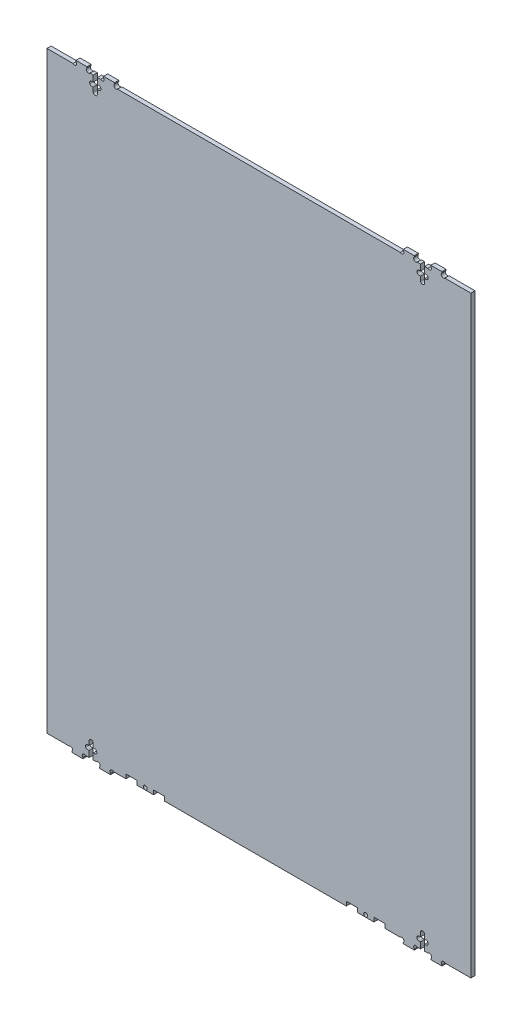
SolidWorks part; units mm, degrees
ref_plane "Спереди" through (0, 0, 0) normal (0, 0, 1) x (1, 0, 0)
ref_plane "Сверху" through (0, 0, 0) normal (0, 1, 0) x (1, 0, 0)
ref_plane "Справа" through (0, 0, 0) normal (1, 0, 0) x (0, 0, -1)
other "Configuration Table"
sketch "Эскиз2" plane through (0, 0, 0) normal (0, 0, 1) x (1, 0, 0)
  line L1 (1138.3, -435.8) -> (518, -435.8)
  line L2 (1138.3, -435.8) -> (1138.3, 435.8)
  line L3 (1138.3, 435.8) -> (518, 435.8)
  line L11 (518, -435.8) -> (518, 435.8)
  dimension "X001" = 518
  dimension "X002" = 1138.3
  dimension "Y001" = 435.8
  dimension "Y002" = 435.8
extrude "Бобышка-Вытянуть1" add sketch "Эскиз2" against normal blind 6
sketch "Стыки_эскиз_пазов_и_стяжек_М5" plane through (0, 0, 0) normal (0, 0, 1) x (1, 0, 0)
  line L0 (1138.4, 429.8) -> (1138.4, 435.8)
  line L1 (1138.4, 435.8) -> (1096.3, 435.8)
  line L2 (1096.3, 435.8) -> (1096.3, 429.8)
  line L3 (1096.3, 429.8) -> (1138.4, 429.8)
  line L4 (678.425, -423.725) -> (678.425, -429.8)
  line L5 (678.425, -429.8) -> (654.575, -429.8)
  line L6 (654.575, -429.8) -> (654.575, -423.725)
  line L7 (654.575, -423.725) -> (638.425, -423.725)
  line L8 (638.425, -423.725) -> (638.425, -429.8)
  line L9 (638.425, -429.8) -> (616, -429.8)
  line L10 (616, -429.8) -> (616, -435.8)
  line L11 (616, -435.8) -> (1040.3, -435.8)
  line L12 (1040.3, -435.8) -> (1040.3, -429.8)
  line L13 (1040.3, -429.8) -> (1013.875, -429.8)
  line L14 (1013.875, -429.8) -> (1013.875, -423.725)
  line L15 (1013.875, -423.725) -> (997.725, -423.725)
  line L16 (997.725, -423.725) -> (997.725, -429.8)
  line L17 (997.725, -429.8) -> (973.875, -429.8)
  line L18 (973.875, -429.8) -> (973.875, -423.725)
  line L19 (973.875, -423.725) -> (957.725, -423.725)
  line L20 (957.725, -423.725) -> (957.725, -429.8)
  line L21 (957.725, -429.8) -> (694.575, -429.8)
  line L22 (694.575, -429.8) -> (694.575, -423.725)
  line L23 (694.575, -423.725) -> (678.425, -423.725)
  line L24 (590.75, -419.95) -> (592.15, -419.95)
  line L25 (592.15, -419.95) -> (592.15, -415.65)
  line L26 (592.15, -415.65) -> (590.75, -415.65)
  line L27 (590.75, -415.65) -> (590.75, -408.8)
  line L28 (590.75, -408.8) -> (585.25, -408.8)
  line L29 (585.25, -408.8) -> (585.25, -415.65)
  line L30 (585.25, -415.65) -> (583.85, -415.65)
  line L31 (583.85, -415.65) -> (583.85, -419.95)
  line L32 (583.85, -419.95) -> (585.25, -419.95)
  line L33 (585.25, -419.95) -> (585.25, -429.8)
  line L34 (585.25, -429.8) -> (576, -429.8)
  line L35 (576, -429.8) -> (576, -435.8)
  line L36 (576, -435.8) -> (585.25, -435.8)
  line L37 (585.25, -435.8) -> (585.25, -435.9)
  line L38 (585.25, -435.9) -> (590.75, -435.9)
  line L39 (590.75, -435.9) -> (590.75, -435.8)
  line L40 (590.75, -435.8) -> (600, -435.8)
  line L41 (600, -435.8) -> (600, -429.8)
  line L42 (600, -429.8) -> (590.75, -429.8)
  line L43 (590.75, -429.8) -> (590.75, -419.95)
  line L44 (518, 435.8) -> (518, -429.8)
  line L45 (518, -429.8) -> (517.9, -429.8)
  line L46 (517.9, -429.8) -> (517.9, -435.8)
  line L47 (517.9, -435.8) -> (560, -435.8)
  line L48 (560, -435.8) -> (560, -429.8)
  line L49 (560, -429.8) -> (524, -429.8)
  line L50 (524, -429.8) -> (524, 429.8)
  line L51 (524, 429.8) -> (566, 429.8)
  line L52 (566, 429.8) -> (566, 435.8)
  line L53 (566, 435.8) -> (518, 435.8)
  line L54 (1040.3, 429.8) -> (1040.3, 435.8)
  line L55 (1040.3, 435.8) -> (622, 435.8)
  line L56 (622, 435.8) -> (622, 429.8)
  line L57 (622, 429.8) -> (1040.3, 429.8)
  line L58 (1065.55, -435.8) -> (1065.55, -435.9)
  line L59 (1065.55, -435.9) -> (1071.05, -435.9)
  line L60 (1071.05, -435.9) -> (1071.05, -435.8)
  line L61 (1071.05, -435.8) -> (1080.3, -435.8)
  line L62 (1080.3, -435.8) -> (1080.3, -429.8)
  line L63 (1080.3, -429.8) -> (1071.05, -429.8)
  line L64 (1071.05, -429.8) -> (1071.05, -419.95)
  line L65 (1071.05, -419.95) -> (1072.45, -419.95)
  line L66 (1072.45, -419.95) -> (1072.45, -415.65)
  line L67 (1072.45, -415.65) -> (1071.05, -415.65)
  line L68 (1071.05, -415.65) -> (1071.05, -408.8)
  line L69 (1071.05, -408.8) -> (1065.55, -408.8)
  line L70 (1065.55, -408.8) -> (1065.55, -415.65)
  line L71 (1065.55, -415.65) -> (1064.15, -415.65)
  line L72 (1064.15, -415.65) -> (1064.15, -419.95)
  line L73 (1064.15, -419.95) -> (1065.55, -419.95)
  line L74 (1065.55, -419.95) -> (1065.55, -429.8)
  line L75 (1065.55, -429.8) -> (1056.3, -429.8)
  line L76 (1056.3, -429.8) -> (1056.3, -435.8)
  line L77 (1056.3, -435.8) -> (1065.55, -435.8)
  line L78 (1071.05, 415.65) -> (1072.45, 415.65)
  line L79 (1072.45, 415.65) -> (1072.45, 419.95)
  line L80 (1072.45, 419.95) -> (1071.05, 419.95)
  line L81 (1071.05, 419.95) -> (1071.05, 429.8)
  line L82 (1071.05, 429.8) -> (1080.3, 429.8)
  line L83 (1080.3, 429.8) -> (1080.3, 435.8)
  line L84 (1080.3, 435.8) -> (1071.05, 435.8)
  line L85 (1071.05, 435.8) -> (1071.05, 435.9)
  line L86 (1071.05, 435.9) -> (1065.55, 435.9)
  line L87 (1065.55, 435.9) -> (1065.55, 435.8)
  line L88 (1065.55, 435.8) -> (1056.3, 435.8)
  line L89 (1056.3, 435.8) -> (1056.3, 429.8)
  line L90 (1056.3, 429.8) -> (1065.55, 429.8)
  line L91 (1065.55, 429.8) -> (1065.55, 419.95)
  line L92 (1065.55, 419.95) -> (1064.15, 419.95)
  line L93 (1064.15, 419.95) -> (1064.15, 415.65)
  line L94 (1064.15, 415.65) -> (1065.55, 415.65)
  line L95 (1065.55, 415.65) -> (1065.55, 408.8)
  line L96 (1065.55, 408.8) -> (1071.05, 408.8)
  line L97 (1071.05, 408.8) -> (1071.05, 415.65)
  line L98 (596.75, 435.8) -> (596.75, 435.9)
  line L99 (596.75, 435.9) -> (591.25, 435.9)
  line L100 (591.25, 435.9) -> (591.25, 435.8)
  line L101 (591.25, 435.8) -> (582, 435.8)
  line L102 (582, 435.8) -> (582, 429.8)
  line L103 (582, 429.8) -> (591.25, 429.8)
  line L104 (591.25, 429.8) -> (591.25, 419.95)
  line L105 (591.25, 419.95) -> (589.85, 419.95)
  line L106 (589.85, 419.95) -> (589.85, 415.65)
  line L107 (589.85, 415.65) -> (591.25, 415.65)
  line L108 (591.25, 415.65) -> (591.25, 408.8)
  line L109 (591.25, 408.8) -> (596.75, 408.8)
  line L110 (596.75, 408.8) -> (596.75, 415.65)
  line L111 (596.75, 415.65) -> (598.15, 415.65)
  line L112 (598.15, 415.65) -> (598.15, 419.95)
  line L113 (598.15, 419.95) -> (596.75, 419.95)
  line L114 (596.75, 419.95) -> (596.75, 429.8)
  line L115 (596.75, 429.8) -> (606, 429.8)
  line L116 (606, 429.8) -> (606, 435.8)
  line L117 (606, 435.8) -> (596.75, 435.8)
  line L118 (1096.3, -435.8) -> (1138.4, -435.8)
  line L119 (1138.4, -435.8) -> (1138.4, -429.8)
  line L120 (1138.4, -429.8) -> (1096.3, -429.8)
  line L121 (1096.3, -429.8) -> (1096.3, -435.8)
  circle A0 centre (666.5, -426.8) radius 2.75
  circle A1 centre (985.8, -426.8) radius 2.75
  dimension "Диаметр001" = 5.5
  dimension "Диаметр002" = 5.5
  dimension "X001" = 517.9
  dimension "X002" = 518
  dimension "X003" = 524
  dimension "X004" = 560
  dimension "X005" = 566
  dimension "X006" = 576
  dimension "X007" = 582
  dimension "X008" = 583.85
  dimension "X009" = 585.25
  dimension "X010" = 589.85
  dimension "X011" = 590.75
  dimension "X012" = 591.25
  dimension "X013" = 592.15
  dimension "X014" = 596.75
  dimension "X015" = 598.15
  dimension "X016" = 600
  dimension "X017" = 606
  dimension "X018" = 616
  dimension "X019" = 622
  dimension "X020" = 638.425
  dimension "X021" = 654.575
  dimension "X022" = 666.5
  dimension "X023" = 678.425
  dimension "X024" = 694.575
  dimension "X025" = 957.725
  dimension "X026" = 973.875
  dimension "X027" = 985.8
  dimension "X028" = 997.725
  dimension "X029" = 1013.875
  dimension "X030" = 1040.3
  dimension "X031" = 1056.3
  dimension "X032" = 1064.15
  dimension "X033" = 1065.55
  dimension "X034" = 1071.05
  dimension "X035" = 1072.45
  dimension "X036" = 1080.3
  dimension "X037" = 1096.3
  dimension "X038" = 1138.4
  dimension "Y001" = 435.9
  dimension "Y002" = 435.8
  dimension "Y003" = 429.8
  dimension "Y004" = 426.8
  dimension "Y005" = 423.725
  dimension "Y006" = 419.95
  dimension "Y007" = 415.65
  dimension "Y008" = 408.8
  dimension "Y009" = 408.8
  dimension "Y010" = 415.65
  dimension "Y011" = 419.95
  dimension "Y012" = 429.8
  dimension "Y013" = 435.8
  dimension "Y014" = 435.9
extrude "Стыки_шип_паз_стяжки_М5" cut sketch "Стыки_эскиз_пазов_и_стяжек_М5" against normal through all and the other way through all
sketch "ЧПУ_М6_01_Центр" plane through (0, 0, 0) normal (0, 0, 1) x (1, 0, 0)
  line L0 (1064.15, -415.65) -> (1064.15, -419.95) construction
  line L1 (1071.05, -419.95) -> (1072.45, -419.95) construction
  point P0 (1068.3, -417.8)
  dimension "От_кромки_по_X" = 4.15
  dimension "От_кромки_по_Y" = 2.15
sketch "ЧПУ_М6_01_Канал_эскиз" plane through (0, 0, 0) normal (0, 0, 1) x (1, 0, 0)
  line L0 (1065.3, -429.9) -> (1071.3, -429.9)
  line L1 (1071.3, -429.9) -> (1071.3, -408.7)
  line L2 (1071.3, -408.7) -> (1065.3, -408.7)
  line L3 (1065.3, -408.7) -> (1065.3, -429.9)
  line L4 (1065.3, -429.9) -> (1071.3, -408.7) construction
  point P4 (1068.3, -419.3)
  dimension "Ширина" = 6
  dimension "Глубина" = 21.2
  dimension "Положение_ОтКромки" = 1.5
extrude "ЧПУ_М6_01_Канал" cut sketch "ЧПУ_М6_01_Канал_эскиз" against normal through all and the other way through all
sketch "ЧПУ_М6_01_Гайка_эскиз" plane through (0, 0, 0) normal (0, 0, 1) x (1, 0, 0)
  line L0 (1063.15, -420.9) -> (1073.45, -420.9)
  line L1 (1073.45, -420.9) -> (1073.45, -414.7)
  line L2 (1073.45, -414.7) -> (1063.15, -414.7)
  line L3 (1063.15, -414.7) -> (1063.15, -420.9)
  line L4 (1063.15, -420.9) -> (1073.45, -414.7) construction
  point P4 (1068.3, -417.8)
  dimension "Ширина" = 10.3
  dimension "Глубина" = 6.2
extrude "ЧПУ_М6_01_Гайка" cut sketch "ЧПУ_М6_01_Гайка_эскиз" against normal through all and the other way through all
sketch "ЧПУ_М6_01_Т_эскиз_1" plane through (0, 0, 0) normal (0, 0, 1) x (1, 0, 0)
  circle A0 centre (1073.45, -417.75) radius 3.05
  circle A1 centre (1063.15, -417.75) radius 3.05
  dimension "Диаметр1" = 6.1
  dimension "Диаметр2" = 6.1
  dimension "Центр1_ПоОси" = 5.15
  dimension "Центр1_ОтКромки" = 0.05
  dimension "Центр2_ПоОси" = 5.15
  dimension "Центр2_ОтКромки" = 0.05
extrude "ЧПУ_М6_01_Т_разгрузка_1" cut sketch "ЧПУ_М6_01_Т_эскиз_1" against normal through all and the other way through all
sketch "ЧПУ_М6_01_Т_эскиз_-1" plane through (0, 0, 0) normal (0, 0, 1) x (1, 0, 0)
  circle A0 centre (1073.45, -417.85) radius 3.05
  circle A1 centre (1063.15, -417.85) radius 3.05
  dimension "Диаметр1" = 6.1
  dimension "Диаметр2" = 6.1
  dimension "Центр1_ПоОси" = 5.15
  dimension "Центр1_ОтКромки" = 0.05
  dimension "Центр2_ПоОси" = 5.15
  dimension "Центр2_ОтКромки" = 0.05
extrude "ЧПУ_М6_01_Т_разгрузка_-1" cut sketch "ЧПУ_М6_01_Т_эскиз_-1" against normal through all and the other way through all
sketch "ЧПУ_М6_01_Конец_эскиз" plane through (0, 0, 0) normal (0, 0, 1) x (1, 0, 0)
  circle A0 centre (1068.3, -408.7) radius 3
  dimension "Центр1_ОтКромки" = 9.1
extrude "ЧПУ_М6_01_Конец" cut sketch "ЧПУ_М6_01_Конец_эскиз" against normal through all and the other way through all
sketch "ЧПУ_М6_02_Центр" plane through (0, 0, 0) normal (0, 0, 1) x (1, 0, 0)
  line L0 (1064.15, 419.95) -> (1064.15, 415.65) construction
  line L1 (1064.15, 415.65) -> (1065.55, 415.65) construction
  point P0 (1068.3, 417.8)
  dimension "От_кромки_по_X" = 4.15
  dimension "От_кромки_по_Y" = 2.15
sketch "ЧПУ_М6_02_Канал_эскиз" plane through (0, 0, 0) normal (0, 0, 1) x (1, 0, 0)
  line L0 (1065.3, 408.7) -> (1071.3, 408.7)
  line L1 (1071.3, 408.7) -> (1071.3, 429.9)
  line L2 (1071.3, 429.9) -> (1065.3, 429.9)
  line L3 (1065.3, 429.9) -> (1065.3, 408.7)
  line L4 (1065.3, 408.7) -> (1071.3, 429.9) construction
  point P4 (1068.3, 419.3)
  dimension "Ширина" = 6
  dimension "Глубина" = 21.2
  dimension "Положение_ОтКромки" = 1.5
extrude "ЧПУ_М6_02_Канал" cut sketch "ЧПУ_М6_02_Канал_эскиз" against normal through all and the other way through all
sketch "ЧПУ_М6_02_Гайка_эскиз" plane through (0, 0, 0) normal (0, 0, 1) x (1, 0, 0)
  line L0 (1063.15, 414.7) -> (1073.45, 414.7)
  line L1 (1073.45, 414.7) -> (1073.45, 420.9)
  line L2 (1073.45, 420.9) -> (1063.15, 420.9)
  line L3 (1063.15, 420.9) -> (1063.15, 414.7)
  line L4 (1063.15, 414.7) -> (1073.45, 420.9) construction
  point P4 (1068.3, 417.8)
  dimension "Ширина" = 10.3
  dimension "Глубина" = 6.2
extrude "ЧПУ_М6_02_Гайка" cut sketch "ЧПУ_М6_02_Гайка_эскиз" against normal through all and the other way through all
sketch "ЧПУ_М6_02_Т_эскиз_1" plane through (0, 0, 0) normal (0, 0, 1) x (1, 0, 0)
  circle A0 centre (1073.45, 417.85) radius 3.05
  circle A1 centre (1063.15, 417.85) radius 3.05
  dimension "Диаметр1" = 6.1
  dimension "Диаметр2" = 6.1
  dimension "Центр1_ПоОси" = 5.15
  dimension "Центр1_ОтКромки" = 0.05
  dimension "Центр2_ПоОси" = 5.15
  dimension "Центр2_ОтКромки" = 0.05
extrude "ЧПУ_М6_02_Т_разгрузка_1" cut sketch "ЧПУ_М6_02_Т_эскиз_1" against normal through all and the other way through all
sketch "ЧПУ_М6_02_Т_эскиз_-1" plane through (0, 0, 0) normal (0, 0, 1) x (1, 0, 0)
  circle A0 centre (1073.45, 417.75) radius 3.05
  circle A1 centre (1063.15, 417.75) radius 3.05
  dimension "Диаметр1" = 6.1
  dimension "Диаметр2" = 6.1
  dimension "Центр1_ПоОси" = 5.15
  dimension "Центр1_ОтКромки" = 0.05
  dimension "Центр2_ПоОси" = 5.15
  dimension "Центр2_ОтКромки" = 0.05
extrude "ЧПУ_М6_02_Т_разгрузка_-1" cut sketch "ЧПУ_М6_02_Т_эскиз_-1" against normal through all and the other way through all
sketch "ЧПУ_М6_02_Конец_эскиз" plane through (0, 0, 0) normal (0, 0, 1) x (1, 0, 0)
  circle A0 centre (1068.3, 408.7) radius 3
  dimension "Центр1_ОтКромки" = 9.1
extrude "ЧПУ_М6_02_Конец" cut sketch "ЧПУ_М6_02_Конец_эскиз" against normal through all and the other way through all
sketch "ЧПУ_М6_03_Центр" plane through (0, 0, 0) normal (0, 0, 1) x (1, 0, 0)
  line L0 (589.85, 419.95) -> (589.85, 415.65) construction
  line L1 (589.85, 415.65) -> (591.25, 415.65) construction
  point P0 (594, 417.8)
  dimension "От_кромки_по_X" = 4.15
  dimension "От_кромки_по_Y" = 2.15
sketch "ЧПУ_М6_03_Канал_эскиз" plane through (0, 0, 0) normal (0, 0, 1) x (1, 0, 0)
  line L0 (591, 408.7) -> (597, 408.7)
  line L1 (597, 408.7) -> (597, 429.9)
  line L2 (597, 429.9) -> (591, 429.9)
  line L3 (591, 429.9) -> (591, 408.7)
  line L4 (591, 408.7) -> (597, 429.9) construction
  point P4 (594, 419.3)
  dimension "Ширина" = 6
  dimension "Глубина" = 21.2
  dimension "Положение_ОтКромки" = 1.5
extrude "ЧПУ_М6_03_Канал" cut sketch "ЧПУ_М6_03_Канал_эскиз" against normal through all and the other way through all
sketch "ЧПУ_М6_03_Гайка_эскиз" plane through (0, 0, 0) normal (0, 0, 1) x (1, 0, 0)
  line L0 (588.85, 414.7) -> (599.15, 414.7)
  line L1 (599.15, 414.7) -> (599.15, 420.9)
  line L2 (599.15, 420.9) -> (588.85, 420.9)
  line L3 (588.85, 420.9) -> (588.85, 414.7)
  line L4 (588.85, 414.7) -> (599.15, 420.9) construction
  point P4 (594, 417.8)
  dimension "Ширина" = 10.3
  dimension "Глубина" = 6.2
extrude "ЧПУ_М6_03_Гайка" cut sketch "ЧПУ_М6_03_Гайка_эскиз" against normal through all and the other way through all
sketch "ЧПУ_М6_03_Т_эскиз_1" plane through (0, 0, 0) normal (0, 0, 1) x (1, 0, 0)
  circle A0 centre (599.15, 417.85) radius 3.05
  circle A1 centre (588.85, 417.85) radius 3.05
  dimension "Диаметр1" = 6.1
  dimension "Диаметр2" = 6.1
  dimension "Центр1_ПоОси" = 5.15
  dimension "Центр1_ОтКромки" = 0.05
  dimension "Центр2_ПоОси" = 5.15
  dimension "Центр2_ОтКромки" = 0.05
extrude "ЧПУ_М6_03_Т_разгрузка_1" cut sketch "ЧПУ_М6_03_Т_эскиз_1" against normal through all and the other way through all
sketch "ЧПУ_М6_03_Т_эскиз_-1" plane through (0, 0, 0) normal (0, 0, 1) x (1, 0, 0)
  circle A0 centre (599.15, 417.75) radius 3.05
  circle A1 centre (588.85, 417.75) radius 3.05
  dimension "Диаметр1" = 6.1
  dimension "Диаметр2" = 6.1
  dimension "Центр1_ПоОси" = 5.15
  dimension "Центр1_ОтКромки" = 0.05
  dimension "Центр2_ПоОси" = 5.15
  dimension "Центр2_ОтКромки" = 0.05
extrude "ЧПУ_М6_03_Т_разгрузка_-1" cut sketch "ЧПУ_М6_03_Т_эскиз_-1" against normal through all and the other way through all
sketch "ЧПУ_М6_03_Конец_эскиз" plane through (0, 0, 0) normal (0, 0, 1) x (1, 0, 0)
  circle A0 centre (594, 408.7) radius 3
  dimension "Центр1_ОтКромки" = 9.1
extrude "ЧПУ_М6_03_Конец" cut sketch "ЧПУ_М6_03_Конец_эскиз" against normal through all and the other way through all
sketch "ЧПУ_М6_04_Центр" plane through (0, 0, 0) normal (0, 0, 1) x (1, 0, 0)
  line L0 (583.85, -415.65) -> (583.85, -419.95) construction
  line L1 (583.85, -419.95) -> (585.25, -419.95) construction
  point P0 (588, -417.8)
  dimension "От_кромки_по_X" = 4.15
  dimension "От_кромки_по_Y" = 2.15
sketch "ЧПУ_М6_04_Канал_эскиз" plane through (0, 0, 0) normal (0, 0, 1) x (1, 0, 0)
  line L0 (585, -429.9) -> (591, -429.9)
  line L1 (591, -429.9) -> (591, -408.7)
  line L2 (591, -408.7) -> (585, -408.7)
  line L3 (585, -408.7) -> (585, -429.9)
  line L4 (585, -429.9) -> (591, -408.7) construction
  point P4 (588, -419.3)
  dimension "Ширина" = 6
  dimension "Глубина" = 21.2
  dimension "Положение_ОтКромки" = 1.5
extrude "ЧПУ_М6_04_Канал" cut sketch "ЧПУ_М6_04_Канал_эскиз" against normal through all and the other way through all
sketch "ЧПУ_М6_04_Гайка_эскиз" plane through (0, 0, 0) normal (0, 0, 1) x (1, 0, 0)
  line L0 (582.85, -420.9) -> (593.15, -420.9)
  line L1 (593.15, -420.9) -> (593.15, -414.7)
  line L2 (593.15, -414.7) -> (582.85, -414.7)
  line L3 (582.85, -414.7) -> (582.85, -420.9)
  line L4 (582.85, -420.9) -> (593.15, -414.7) construction
  point P4 (588, -417.8)
  dimension "Ширина" = 10.3
  dimension "Глубина" = 6.2
extrude "ЧПУ_М6_04_Гайка" cut sketch "ЧПУ_М6_04_Гайка_эскиз" against normal through all and the other way through all
sketch "ЧПУ_М6_04_Т_эскиз_1" plane through (0, 0, 0) normal (0, 0, 1) x (1, 0, 0)
  circle A0 centre (593.15, -417.75) radius 3.05
  circle A1 centre (582.85, -417.75) radius 3.05
  dimension "Диаметр1" = 6.1
  dimension "Диаметр2" = 6.1
  dimension "Центр1_ПоОси" = 5.15
  dimension "Центр1_ОтКромки" = 0.05
  dimension "Центр2_ПоОси" = 5.15
  dimension "Центр2_ОтКромки" = 0.05
extrude "ЧПУ_М6_04_Т_разгрузка_1" cut sketch "ЧПУ_М6_04_Т_эскиз_1" against normal through all and the other way through all
sketch "ЧПУ_М6_04_Т_эскиз_-1" plane through (0, 0, 0) normal (0, 0, 1) x (1, 0, 0)
  circle A0 centre (593.15, -417.85) radius 3.05
  circle A1 centre (582.85, -417.85) radius 3.05
  dimension "Диаметр1" = 6.1
  dimension "Диаметр2" = 6.1
  dimension "Центр1_ПоОси" = 5.15
  dimension "Центр1_ОтКромки" = 0.05
  dimension "Центр2_ПоОси" = 5.15
  dimension "Центр2_ОтКромки" = 0.05
extrude "ЧПУ_М6_04_Т_разгрузка_-1" cut sketch "ЧПУ_М6_04_Т_эскиз_-1" against normal through all and the other way through all
sketch "ЧПУ_М6_04_Конец_эскиз" plane through (0, 0, 0) normal (0, 0, 1) x (1, 0, 0)
  circle A0 centre (588, -408.7) radius 3
  dimension "Центр1_ОтКромки" = 9.1
extrude "ЧПУ_М6_04_Конец" cut sketch "ЧПУ_М6_04_Конец_эскиз" against normal through all and the other way through all
sketch "ЧПУ_Шаблон_углов_01" plane through (0, 0, 0) normal (0, 0, 1) x (1, 0, 0)
  line L0 (1056.3, -429.8) -> (1056.3, -435.8) construction
  line L1 (1065.3, -429.8) -> (1056.3, -429.8) construction
  line L2 (1096.3, -429.8) -> (1096.3, -435.8) construction
  line L3 (1138.3, -429.8) -> (1096.3, -429.8) construction
  line L4 (576, -429.8) -> (576, -435.8) construction
  line L5 (585, -429.8) -> (576, -429.8) construction
  line L6 (616, -429.8) -> (616, -435.8) construction
  line L7 (638.425, -429.8) -> (616, -429.8) construction
  circle A0 centre (1058.4213, -431.9213) radius 3.05
  circle A1 centre (1098.4213, -431.9213) radius 3.05
  circle A2 centre (578.1213, -431.9213) radius 3.05
  circle A3 centre (618.1213, -431.9213) radius 3.05
  dimension "D3" = 6.1
  dimension "D6" = 6.1
  dimension "D9" = 6.1
  dimension "D12" = 6.1
  dimension "D1" = 2.1213
  dimension "D2" = 2.1213
  dimension "D4" = 2.1213
  dimension "D5" = 2.1213
  dimension "D7" = 2.1213
  dimension "D8" = 2.1213
  dimension "D10" = 2.1213
  dimension "D11" = 2.1213
sketch "ЧПУ_Шаблон_углов_02" plane through (0, 0, 0) normal (0, 0, 1) x (1, 0, 0)
  line L0 (1080.3, -435.8) -> (1080.3, -429.8) construction
  line L1 (1080.3, -429.8) -> (1071.3, -429.8) construction
  line L2 (560, -435.8) -> (560, -429.8) construction
  line L3 (560, -429.8) -> (524, -429.8) construction
  line L4 (600, -435.8) -> (600, -429.8) construction
  line L5 (600, -429.8) -> (591, -429.8) construction
  line L6 (1040.3, -435.8) -> (1040.3, -429.8) construction
  line L7 (1040.3, -429.8) -> (1013.875, -429.8) construction
  circle A0 centre (1078.1787, -431.9213) radius 3.05
  circle A1 centre (557.8787, -431.9213) radius 3.05
  circle A2 centre (597.8787, -431.9213) radius 3.05
  circle A3 centre (1038.1787, -431.9213) radius 3.05
  dimension "D3" = 6.1
  dimension "D6" = 6.1
  dimension "D9" = 6.1
  dimension "D12" = 6.1
  dimension "D1" = 2.1213
  dimension "D2" = 2.1213
  dimension "D4" = 2.1213
  dimension "D5" = 2.1213
  dimension "D7" = 2.1213
  dimension "D8" = 2.1213
  dimension "D10" = 2.1213
  dimension "D11" = 2.1213
sketch "ЧПУ_Шаблон_углов_03" plane through (0, 0, 0) normal (0, 0, 1) x (1, 0, 0)
  line L0 (1096.3, 435.8) -> (1096.3, 429.8) construction
  line L1 (1096.3, 429.8) -> (1138.3, 429.8) construction
  line L2 (1056.3, 435.8) -> (1056.3, 429.8) construction
  line L3 (1056.3, 429.8) -> (1065.3, 429.8) construction
  line L4 (622, 435.8) -> (622, 429.8) construction
  line L5 (622, 429.8) -> (1040.3, 429.8) construction
  line L6 (582, 435.8) -> (582, 429.8) construction
  line L7 (582, 429.8) -> (591, 429.8) construction
  circle A0 centre (1098.4213, 431.9213) radius 3.05
  circle A1 centre (1058.4213, 431.9213) radius 3.05
  circle A2 centre (624.1213, 431.9213) radius 3.05
  circle A3 centre (584.1213, 431.9213) radius 3.05
  dimension "D3" = 6.1
  dimension "D6" = 6.1
  dimension "D9" = 6.1
  dimension "D12" = 6.1
  dimension "D1" = 2.1213
  dimension "D2" = 2.1213
  dimension "D4" = 2.1213
  dimension "D5" = 2.1213
  dimension "D7" = 2.1213
  dimension "D8" = 2.1213
  dimension "D10" = 2.1213
  dimension "D11" = 2.1213
sketch "ЧПУ_Шаблон_углов_04" plane through (0, 0, 0) normal (0, 0, 1) x (1, 0, 0)
  line L0 (1080.3, 429.8) -> (1080.3, 435.8) construction
  line L1 (1071.3, 429.8) -> (1080.3, 429.8) construction
  line L2 (1040.3, 429.8) -> (1040.3, 435.8) construction
  line L3 (622, 429.8) -> (1040.3, 429.8) construction
  line L4 (606, 429.8) -> (606, 435.8) construction
  line L5 (597, 429.8) -> (606, 429.8) construction
  line L6 (566, 429.8) -> (566, 435.8) construction
  line L7 (524, 429.8) -> (566, 429.8) construction
  circle A0 centre (1078.1787, 431.9213) radius 3.05
  circle A1 centre (1038.1787, 431.9213) radius 3.05
  circle A2 centre (603.8787, 431.9213) radius 3.05
  circle A3 centre (563.8787, 431.9213) radius 3.05
  dimension "D3" = 6.1
  dimension "D6" = 6.1
  dimension "D9" = 6.1
  dimension "D12" = 6.1
  dimension "D1" = 2.1213
  dimension "D2" = 2.1213
  dimension "D4" = 2.1213
  dimension "D5" = 2.1213
  dimension "D7" = 2.1213
  dimension "D8" = 2.1213
  dimension "D10" = 2.1213
  dimension "D11" = 2.1213
extrude "ЧПУ_Разгрузки_01" cut sketch "ЧПУ_Шаблон_углов_01" against normal through all and the other way through all
extrude "ЧПУ_Разгрузки_02" cut sketch "ЧПУ_Шаблон_углов_02" against normal through all and the other way through all
extrude "ЧПУ_Разгрузки_03" cut sketch "ЧПУ_Шаблон_углов_03" against normal through all and the other way through all
extrude "ЧПУ_Разгрузки_04" cut sketch "ЧПУ_Шаблон_углов_04" against normal through all and the other way through all
equation "\"Ширина груза\"= 420"
equation "\"Глубина груза\"= 490"
equation "\"Высота груза\"= 297"
equation "\"Ширина ячейки\"= \"Ширина груза\" + 10"
equation "\"Глубина ячейки\"= \"Глубина груза\" + 10"
equation "\"Высота ячейки\"= \"Высота груза\" + 10 + 13"
equation "\"Колво ячеек ширина\"= 2"
equation "\"Колво ячеек высота\"= 2"
equation "\"Толщина стенки\" = 6"
equation "\"Крепление дверцы\"= 5 "
equation "\"Ширина рейки\"= \"Толщина шестерни\""
equation "\"Высота рейки\"= 20"
equation "\"Высота пола\"= \"Толщина стенки\" * 2"
equation "\"Колво полозьев\"= 5"
equation "\"Отступ рейки\"= 20"
equation "\"Глубина каретки\"= \"Глубина ячейки\" + 30 + \"Мотор Y высота корпуса\" + 20"
equation "\"Длинна рейки\" = (\"Ширина ячейки\" + \"Толщина стенки\" + \"Крепление дверцы\") * \"Колво ячеек ширина\" + \"Ширина ячейки выгрузки\" * \"Колво выгрузки\" + \"Толщина стенки\" + \"Отступ крепления мотора фиксации\" * 2 - \"Крепление дверцы\" * \"Колво ячеек ширина\""
equation "\"Отступ шпильки\"= 26"
equation "\"Диаметр шпильки\"= 5"
equation "\"Длинна шпильки\"= ( \"Высота ячейки\" + \"Толщина стенки\" + \"Высота пола\" ) * \"Колво ячеек высота\" + ( \"Толщина стенки\" + \"Отступ рейки\" ) * 2 "
equation "\"Ширина пластины\"= 50  "
equation "\"Высота зона выгрузки\"= \"Высота ячейки\" * 2 + \"Толщина стенки\" * 2"
equation "\"Колво выгрузки\"= 1"
equation "\"Ширина ячейки выгрузки\"= \"Ширина ячейки\" + \"Толщина стенки\" + \"Отступ крепления мотора фиксации\"*2"
equation "\"Отступ крепления мотора фиксации\" = (\"Ширина пластины\" + 20 - \"Толщина стенки\") / 2"
equation "\"Мотор X ширина корпуса\"= 42.3"
equation "\"Мотор X высота корпуса\"= 42.3"
equation "\"Мотор X длина корпуса\"= 40"
equation "\"Мотор X вылет вала\"= 19.8"
equation "\"Мотор Y ширина корпуса\"= 42.3"
equation "\"Мотор Y высота корпуса\"= 42.3"
equation "\"Мотор Y длина корпуса\"= 48"
equation "\"Мотор Y вылет вала\"= 30"
equation "\"Мотор Z ширина корпуса\"= 42"
equation "\"Мотор Z высота корпуса\"= 42"
equation "\"Мотор Z длина корпуса\"= 40"
equation "\"Мотор Z вылет вала\"= 23"
equation "\"Мотор диаметр вала ПРЕДВ\"= 5"
equation "\"Мотор шаг крепления ПРЕДВ\"= 31"
equation "\"Мотор диаметр отверстий ПРЕДВ\"= 3"
equation "\"Мотор глубина отверстий ПРЕДВ\"= 4.5"
equation "\"Мотор диаметр буртика ПРЕДВ\"= 22"
equation "\"Мотор высота буртика ПРЕДВ\"= 2"
equation "\"Мотор диаметр шкива ПРЕДВ\"= 16"
equation "\"Мотор длина шкива ПРЕДВ\"= 12"
equation "\"Мотор отступ шкива ПРЕДВ\"= 5"
equation "\"Мотор X шаг градусов\"= 1.8"
equation "\"Мотор Y шаг градусов\"= 1.8"
equation "\"Мотор Z шаг градусов\"= 1.8"
equation "\"Мотор Y диаметр ротора\"= 25.78"
equation "\"Толщина шестерни\"= 10"
equation "\"D1@Бобышка-Вытянуть1\"=\"Толщина стенки\""
equation "\"Фреза стыка\"= 6"
equation "\"Перебег разгрузки\"= 0.05"
equation "\"Канал М6\"=6"
equation "\"Гайка под ключ\"=10.3"
equation "\"Длина кармана гайки\"=6.2"
equation "\"Основная фреза\"=6"
equation "\"Запас разгрузки\"=0.05"
equation "\"Ширина@ЧПУ_М6_01_Канал_эскиз\" = \"Канал М6\""
equation "\"Глубина@ЧПУ_М6_01_Канал_эскиз\" = 21.2"
equation "\"Положение_ОтКромки@ЧПУ_М6_01_Канал_эскиз\" = - (-1.5)"
equation "\"Ширина@ЧПУ_М6_01_Гайка_эскиз\" = \"Гайка под ключ\""
equation "\"Глубина@ЧПУ_М6_01_Гайка_эскиз\" = \"Длина кармана гайки\""
equation "\"Центр1_ПоОси@ЧПУ_М6_01_Т_эскиз_1\" = (\"Гайка под ключ\"/2)"
equation "\"Центр1_ОтКромки@ЧПУ_М6_01_Т_эскиз_1\" = (0.05)"
equation "\"Диаметр1@ЧПУ_М6_01_Т_эскиз_1\" = \"Основная фреза\"+2*\"Запас разгрузки\""
equation "\"Центр2_ПоОси@ЧПУ_М6_01_Т_эскиз_1\" = - (-\"Гайка под ключ\"/2)"
equation "\"Центр2_ОтКромки@ЧПУ_М6_01_Т_эскиз_1\" = (0.05)"
equation "\"Диаметр2@ЧПУ_М6_01_Т_эскиз_1\" = \"Основная фреза\"+2*\"Запас разгрузки\""
equation "\"Центр1_ПоОси@ЧПУ_М6_01_Т_эскиз_-1\" = (\"Гайка под ключ\"/2)"
equation "\"Центр1_ОтКромки@ЧПУ_М6_01_Т_эскиз_-1\" = - (-0.05)"
equation "\"Диаметр1@ЧПУ_М6_01_Т_эскиз_-1\" = \"Основная фреза\"+2*\"Запас разгрузки\""
equation "\"Центр2_ПоОси@ЧПУ_М6_01_Т_эскиз_-1\" = - (-\"Гайка под ключ\"/2)"
equation "\"Центр2_ОтКромки@ЧПУ_М6_01_Т_эскиз_-1\" = - (-0.05)"
equation "\"Диаметр2@ЧПУ_М6_01_Т_эскиз_-1\" = \"Основная фреза\"+2*\"Запас разгрузки\""
equation "\"Центр1_ОтКромки@ЧПУ_М6_01_Конец_эскиз\" = (9.1)"
equation "\"Диаметр1@ЧПУ_М6_01_Конец_эскиз\" = \"Канал М6\""
equation "\"Ширина@ЧПУ_М6_02_Канал_эскиз\" = \"Канал М6\""
equation "\"Глубина@ЧПУ_М6_02_Канал_эскиз\" = 21.2"
equation "\"Положение_ОтКромки@ЧПУ_М6_02_Канал_эскиз\" = (1.5)"
equation "\"Ширина@ЧПУ_М6_02_Гайка_эскиз\" = \"Гайка под ключ\""
equation "\"Глубина@ЧПУ_М6_02_Гайка_эскиз\" = \"Длина кармана гайки\""
equation "\"Центр1_ПоОси@ЧПУ_М6_02_Т_эскиз_1\" = (\"Гайка под ключ\"/2)"
equation "\"Центр1_ОтКромки@ЧПУ_М6_02_Т_эскиз_1\" = (0.05)"
equation "\"Диаметр1@ЧПУ_М6_02_Т_эскиз_1\" = \"Основная фреза\"+2*\"Запас разгрузки\""
equation "\"Центр2_ПоОси@ЧПУ_М6_02_Т_эскиз_1\" = - (-\"Гайка под ключ\"/2)"
equation "\"Центр2_ОтКромки@ЧПУ_М6_02_Т_эскиз_1\" = (0.05)"
equation "\"Диаметр2@ЧПУ_М6_02_Т_эскиз_1\" = \"Основная фреза\"+2*\"Запас разгрузки\""
equation "\"Центр1_ПоОси@ЧПУ_М6_02_Т_эскиз_-1\" = (\"Гайка под ключ\"/2)"
equation "\"Центр1_ОтКромки@ЧПУ_М6_02_Т_эскиз_-1\" = - (-0.05)"
equation "\"Диаметр1@ЧПУ_М6_02_Т_эскиз_-1\" = \"Основная фреза\"+2*\"Запас разгрузки\""
equation "\"Центр2_ПоОси@ЧПУ_М6_02_Т_эскиз_-1\" = - (-\"Гайка под ключ\"/2)"
equation "\"Центр2_ОтКромки@ЧПУ_М6_02_Т_эскиз_-1\" = - (-0.05)"
equation "\"Диаметр2@ЧПУ_М6_02_Т_эскиз_-1\" = \"Основная фреза\"+2*\"Запас разгрузки\""
equation "\"Центр1_ОтКромки@ЧПУ_М6_02_Конец_эскиз\" = - (-9.1)"
equation "\"Диаметр1@ЧПУ_М6_02_Конец_эскиз\" = \"Канал М6\""
equation "\"Ширина@ЧПУ_М6_03_Канал_эскиз\" = \"Канал М6\""
equation "\"Глубина@ЧПУ_М6_03_Канал_эскиз\" = 21.2"
equation "\"Положение_ОтКромки@ЧПУ_М6_03_Канал_эскиз\" = (1.5)"
equation "\"Ширина@ЧПУ_М6_03_Гайка_эскиз\" = \"Гайка под ключ\""
equation "\"Глубина@ЧПУ_М6_03_Гайка_эскиз\" = \"Длина кармана гайки\""
equation "\"Центр1_ПоОси@ЧПУ_М6_03_Т_эскиз_1\" = (\"Гайка под ключ\"/2)"
equation "\"Центр1_ОтКромки@ЧПУ_М6_03_Т_эскиз_1\" = (0.05)"
equation "\"Диаметр1@ЧПУ_М6_03_Т_эскиз_1\" = \"Основная фреза\"+2*\"Запас разгрузки\""
equation "\"Центр2_ПоОси@ЧПУ_М6_03_Т_эскиз_1\" = - (-\"Гайка под ключ\"/2)"
equation "\"Центр2_ОтКромки@ЧПУ_М6_03_Т_эскиз_1\" = (0.05)"
equation "\"Диаметр2@ЧПУ_М6_03_Т_эскиз_1\" = \"Основная фреза\"+2*\"Запас разгрузки\""
equation "\"Центр1_ПоОси@ЧПУ_М6_03_Т_эскиз_-1\" = (\"Гайка под ключ\"/2)"
equation "\"Центр1_ОтКромки@ЧПУ_М6_03_Т_эскиз_-1\" = - (-0.05)"
equation "\"Диаметр1@ЧПУ_М6_03_Т_эскиз_-1\" = \"Основная фреза\"+2*\"Запас разгрузки\""
equation "\"Центр2_ПоОси@ЧПУ_М6_03_Т_эскиз_-1\" = - (-\"Гайка под ключ\"/2)"
equation "\"Центр2_ОтКромки@ЧПУ_М6_03_Т_эскиз_-1\" = - (-0.05)"
equation "\"Диаметр2@ЧПУ_М6_03_Т_эскиз_-1\" = \"Основная фреза\"+2*\"Запас разгрузки\""
equation "\"Центр1_ОтКромки@ЧПУ_М6_03_Конец_эскиз\" = - (-9.1)"
equation "\"Диаметр1@ЧПУ_М6_03_Конец_эскиз\" = \"Канал М6\""
equation "\"Ширина@ЧПУ_М6_04_Канал_эскиз\" = \"Канал М6\""
equation "\"Глубина@ЧПУ_М6_04_Канал_эскиз\" = 21.2"
equation "\"Положение_ОтКромки@ЧПУ_М6_04_Канал_эскиз\" = - (-1.5)"
equation "\"Ширина@ЧПУ_М6_04_Гайка_эскиз\" = \"Гайка под ключ\""
equation "\"Глубина@ЧПУ_М6_04_Гайка_эскиз\" = \"Длина кармана гайки\""
equation "\"Центр1_ПоОси@ЧПУ_М6_04_Т_эскиз_1\" = (\"Гайка под ключ\"/2)"
equation "\"Центр1_ОтКромки@ЧПУ_М6_04_Т_эскиз_1\" = (0.05)"
equation "\"Диаметр1@ЧПУ_М6_04_Т_эскиз_1\" = \"Основная фреза\"+2*\"Запас разгрузки\""
equation "\"Центр2_ПоОси@ЧПУ_М6_04_Т_эскиз_1\" = - (-\"Гайка под ключ\"/2)"
equation "\"Центр2_ОтКромки@ЧПУ_М6_04_Т_эскиз_1\" = (0.05)"
equation "\"Диаметр2@ЧПУ_М6_04_Т_эскиз_1\" = \"Основная фреза\"+2*\"Запас разгрузки\""
equation "\"Центр1_ПоОси@ЧПУ_М6_04_Т_эскиз_-1\" = (\"Гайка под ключ\"/2)"
equation "\"Центр1_ОтКромки@ЧПУ_М6_04_Т_эскиз_-1\" = - (-0.05)"
equation "\"Диаметр1@ЧПУ_М6_04_Т_эскиз_-1\" = \"Основная фреза\"+2*\"Запас разгрузки\""
equation "\"Центр2_ПоОси@ЧПУ_М6_04_Т_эскиз_-1\" = - (-\"Гайка под ключ\"/2)"
equation "\"Центр2_ОтКромки@ЧПУ_М6_04_Т_эскиз_-1\" = - (-0.05)"
equation "\"Диаметр2@ЧПУ_М6_04_Т_эскиз_-1\" = \"Основная фреза\"+2*\"Запас разгрузки\""
equation "\"Центр1_ОтКромки@ЧПУ_М6_04_Конец_эскиз\" = (9.1)"
equation "\"Диаметр1@ЧПУ_М6_04_Конец_эскиз\" = \"Канал М6\""
equation "\"D1@ЧПУ_Шаблон_углов_01\" = \"Фреза стыка\"/(2*sqr(2))"
equation "\"D2@ЧПУ_Шаблон_углов_01\" = \"Фреза стыка\"/(2*sqr(2))"
equation "\"D3@ЧПУ_Шаблон_углов_01\" = \"Фреза стыка\"+2*\"Перебег разгрузки\""
equation "\"D4@ЧПУ_Шаблон_углов_01\" = \"Фреза стыка\"/(2*sqr(2))"
equation "\"D5@ЧПУ_Шаблон_углов_01\" = \"Фреза стыка\"/(2*sqr(2))"
equation "\"D6@ЧПУ_Шаблон_углов_01\" = \"Фреза стыка\"+2*\"Перебег разгрузки\""
equation "\"D7@ЧПУ_Шаблон_углов_01\" = \"Фреза стыка\"/(2*sqr(2))"
equation "\"D8@ЧПУ_Шаблон_углов_01\" = \"Фреза стыка\"/(2*sqr(2))"
equation "\"D9@ЧПУ_Шаблон_углов_01\" = \"Фреза стыка\"+2*\"Перебег разгрузки\""
equation "\"D10@ЧПУ_Шаблон_углов_01\" = \"Фреза стыка\"/(2*sqr(2))"
equation "\"D11@ЧПУ_Шаблон_углов_01\" = \"Фреза стыка\"/(2*sqr(2))"
equation "\"D12@ЧПУ_Шаблон_углов_01\" = \"Фреза стыка\"+2*\"Перебег разгрузки\""
equation "\"D1@ЧПУ_Шаблон_углов_02\" = \"Фреза стыка\"/(2*sqr(2))"
equation "\"D2@ЧПУ_Шаблон_углов_02\" = \"Фреза стыка\"/(2*sqr(2))"
equation "\"D3@ЧПУ_Шаблон_углов_02\" = \"Фреза стыка\"+2*\"Перебег разгрузки\""
equation "\"D4@ЧПУ_Шаблон_углов_02\" = \"Фреза стыка\"/(2*sqr(2))"
equation "\"D5@ЧПУ_Шаблон_углов_02\" = \"Фреза стыка\"/(2*sqr(2))"
equation "\"D6@ЧПУ_Шаблон_углов_02\" = \"Фреза стыка\"+2*\"Перебег разгрузки\""
equation "\"D7@ЧПУ_Шаблон_углов_02\" = \"Фреза стыка\"/(2*sqr(2))"
equation "\"D8@ЧПУ_Шаблон_углов_02\" = \"Фреза стыка\"/(2*sqr(2))"
equation "\"D9@ЧПУ_Шаблон_углов_02\" = \"Фреза стыка\"+2*\"Перебег разгрузки\""
equation "\"D10@ЧПУ_Шаблон_углов_02\" = \"Фреза стыка\"/(2*sqr(2))"
equation "\"D11@ЧПУ_Шаблон_углов_02\" = \"Фреза стыка\"/(2*sqr(2))"
equation "\"D12@ЧПУ_Шаблон_углов_02\" = \"Фреза стыка\"+2*\"Перебег разгрузки\""
equation "\"D1@ЧПУ_Шаблон_углов_03\" = \"Фреза стыка\"/(2*sqr(2))"
equation "\"D2@ЧПУ_Шаблон_углов_03\" = \"Фреза стыка\"/(2*sqr(2))"
equation "\"D3@ЧПУ_Шаблон_углов_03\" = \"Фреза стыка\"+2*\"Перебег разгрузки\""
equation "\"D4@ЧПУ_Шаблон_углов_03\" = \"Фреза стыка\"/(2*sqr(2))"
equation "\"D5@ЧПУ_Шаблон_углов_03\" = \"Фреза стыка\"/(2*sqr(2))"
equation "\"D6@ЧПУ_Шаблон_углов_03\" = \"Фреза стыка\"+2*\"Перебег разгрузки\""
equation "\"D7@ЧПУ_Шаблон_углов_03\" = \"Фреза стыка\"/(2*sqr(2))"
equation "\"D8@ЧПУ_Шаблон_углов_03\" = \"Фреза стыка\"/(2*sqr(2))"
equation "\"D9@ЧПУ_Шаблон_углов_03\" = \"Фреза стыка\"+2*\"Перебег разгрузки\""
equation "\"D10@ЧПУ_Шаблон_углов_03\" = \"Фреза стыка\"/(2*sqr(2))"
equation "\"D11@ЧПУ_Шаблон_углов_03\" = \"Фреза стыка\"/(2*sqr(2))"
equation "\"D12@ЧПУ_Шаблон_углов_03\" = \"Фреза стыка\"+2*\"Перебег разгрузки\""
equation "\"D1@ЧПУ_Шаблон_углов_04\" = \"Фреза стыка\"/(2*sqr(2))"
equation "\"D2@ЧПУ_Шаблон_углов_04\" = \"Фреза стыка\"/(2*sqr(2))"
equation "\"D3@ЧПУ_Шаблон_углов_04\" = \"Фреза стыка\"+2*\"Перебег разгрузки\""
equation "\"D4@ЧПУ_Шаблон_углов_04\" = \"Фреза стыка\"/(2*sqr(2))"
equation "\"D5@ЧПУ_Шаблон_углов_04\" = \"Фреза стыка\"/(2*sqr(2))"
equation "\"D6@ЧПУ_Шаблон_углов_04\" = \"Фреза стыка\"+2*\"Перебег разгрузки\""
equation "\"D7@ЧПУ_Шаблон_углов_04\" = \"Фреза стыка\"/(2*sqr(2))"
equation "\"D8@ЧПУ_Шаблон_углов_04\" = \"Фреза стыка\"/(2*sqr(2))"
equation "\"D9@ЧПУ_Шаблон_углов_04\" = \"Фреза стыка\"+2*\"Перебег разгрузки\""
equation "\"D10@ЧПУ_Шаблон_углов_04\" = \"Фреза стыка\"/(2*sqr(2))"
equation "\"D11@ЧПУ_Шаблон_углов_04\" = \"Фреза стыка\"/(2*sqr(2))"
equation "\"D12@ЧПУ_Шаблон_углов_04\" = \"Фреза стыка\"+2*\"Перебег разгрузки\""
